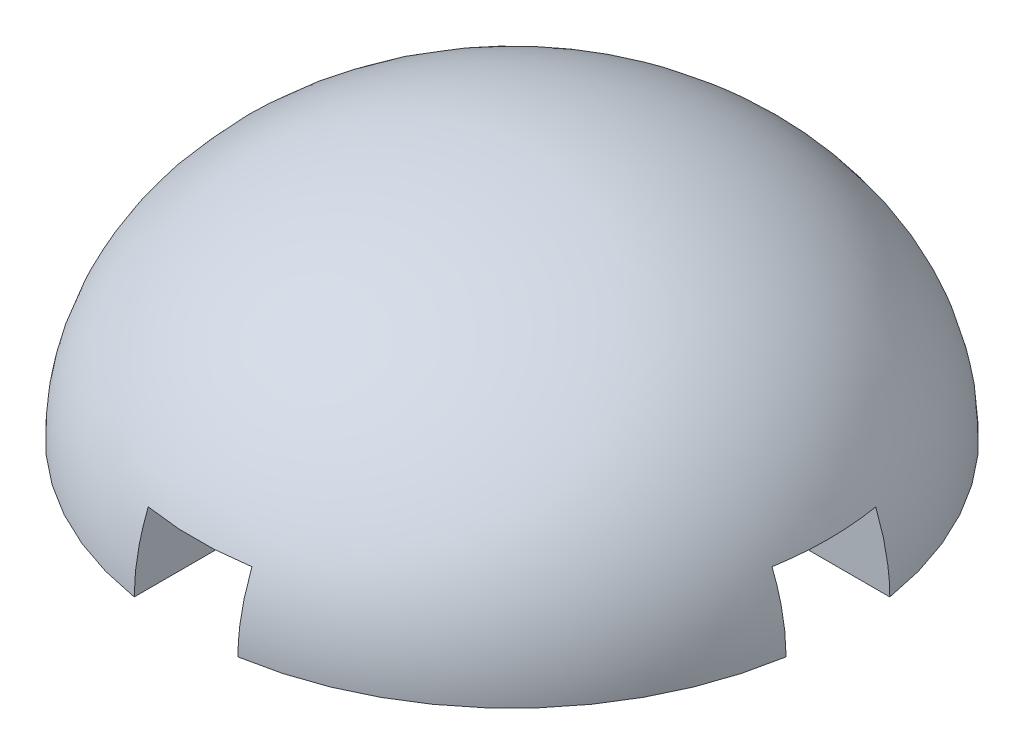
SolidWorks part; units mm, degrees
ref_plane "Front Plane" through (0, 0, 0) normal (0, 0, 1) x (1, 0, 0)
ref_plane "Top Plane" through (0, 0, 0) normal (0, 1, 0) x (1, 0, 0)
ref_plane "Right Plane" through (0, 0, 0) normal (1, 0, 0) x (0, 0, -1)
sketch "Sketch2" plane through (0, 0, 0) normal (0, 0, 1) x (1, 0, 0)
  line L0 (0, 0) -> (0, 17.5)
  line L2 (17.5, 0) -> (0, 0)
  arc A0 (17.5, 0) -> (0, 17.5) centre (0, 0) ccw
  dimension "D1" = 35
revolve "Revolve1" add sketch "Sketch2" angle 360 about L0
scale "Scale1" scale about centroid uniform scaling no x scale factor 1 y scale factor 0.75 z scale factor 1
ref_axis "Axis1" through (0, 0.9844, 0) along (0, 1, 0)
sketch "Sketch3" plane through (0, 0, 0) normal (0, 0, 1) x (1, 0, 0)
  line L3 (-2.75, 5.4063) -> (-2.75, 1.6406)
  line L9 (-2.75, 5.4063) -> (2.75, 5.4063)
  line L18 (-17.5, 1.6406) -> (17.5, 1.6406) construction
  line L19 (2.75, 1.6406) -> (2.75, 5.4063)
  line L20 (2.75, 1.6406) -> (-2.75, 1.6406)
  point P5 (-3.3894, 1.4063)
  point P9 (0.2443, 1.4063)
  point P11 (0, 5.4063)
  point P12 (0.2443, 1.4063)
  point P14 (0, 5.4063)
  dimension "D1" = 5.5
extrude "Cut-Extrude1" cut sketch "Sketch3" along normal mid plane 35
pattern_circular "CirPattern1" count 2 every 90 about axis through (0, 0.9844, 0) along (0, 1, 0) of "Cut-Extrude1"
sketch "Sketch4" plane through (0, 5.4063, 0) normal (0, -1, 0) x (1, 0, 0)
  circle A0 centre (0, 0) radius 2.5
  circle A1 centre (0, 0) radius 0.625
  dimension "D1" = 5
  dimension "D2" = 1.25
extrude "Boss-Extrude1" add sketch "Sketch4" along normal up to surface (3.7656 mm away) up to face at (8.3802, 1.6406, 8.3802)
